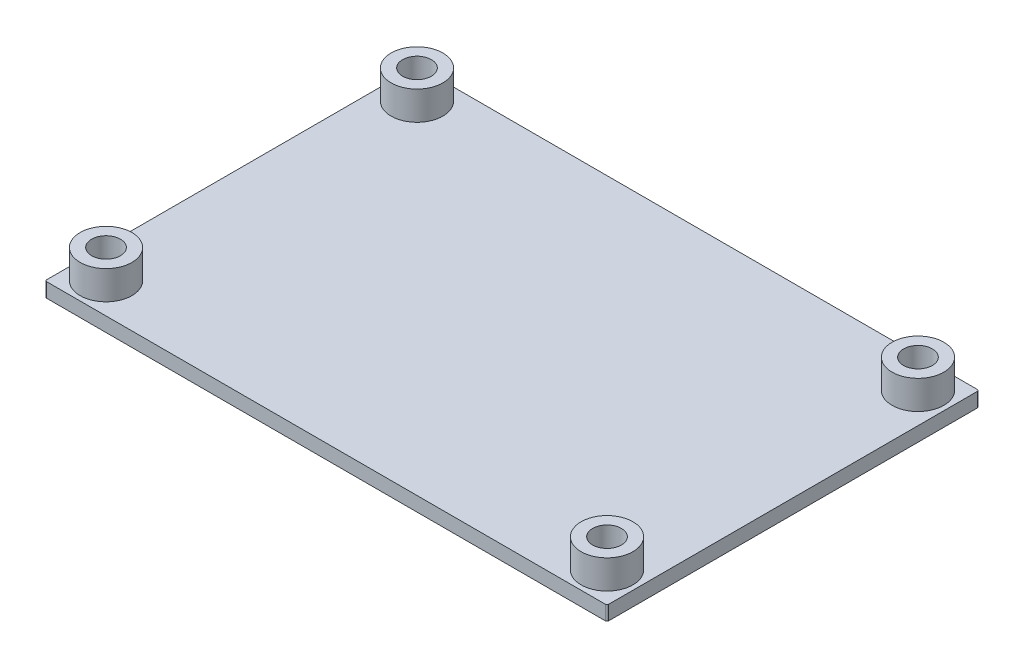
SolidWorks part; units mm, degrees
ref_plane "Front Plane" through (0, 0, 0) normal (0, 0, 1) x (1, 0, 0)
ref_plane "Top Plane" through (0, 0, 0) normal (0, 1, 0) x (1, 0, 0)
ref_plane "Right Plane" through (0, 0, 0) normal (1, 0, 0) x (0, 0, -1)
sketch "Sketch2" plane through (0, 0, 0) normal (0, 1, 0) x (1, 0, 0)
  line L0 (100.3, 3) -> (100.3, 67)
  line L1 (3, 0) -> (100, 0)
  line L2 (0, 3) -> (0, 67)
  line L3 (3, 70) -> (100, 70)
  line L4 (103, 3) -> (103, 67)
  line L5 (3, 67.3) -> (100, 67.3)
  line L6 (2.7, 3) -> (2.7, 67)
  line L7 (3, 2.7) -> (100, 2.7)
  line L8 (103, 35) -> (0, 35) construction
  line L9 (51.5, 70) -> (51.5, 0) construction
  arc A0 (0, 67) -> (3, 70) centre (3, 67) cw
  arc A1 (3, 0) -> (0, 3) centre (3, 3) cw
  arc A2 (100, 0) -> (103, 3) centre (100, 3) ccw
  arc A3 (100, 70) -> (103, 67) centre (100, 67) cw
  arc A4 (100, 67.3) -> (100.3, 67) centre (100, 67) cw
  arc A5 (2.7, 67) -> (3, 67.3) centre (3, 67) cw
  arc A6 (3, 2.7) -> (2.7, 3) centre (3, 3) cw
  arc A7 (100, 2.7) -> (100.3, 3) centre (100, 3) ccw
  circle A8 centre (95, 8) radius 2.5
  circle A9 centre (95, 8) radius 4.5
  circle A10 centre (95, 62) radius 2.5
  circle A11 centre (95, 62) radius 4.5
  circle A12 centre (8, 62) radius 4.5
  circle A13 centre (8, 62) radius 2.5
  circle A14 centre (8, 8) radius 2.5
  circle A15 centre (8, 8) radius 4.5
  point P9 (0, 0)
  point P12 (103, 0)
  point P15 (103, 70)
  dimension "D3" = 3
  dimension "D5" = 2
  dimension "D6" = 8
  dimension "D1" = 70
  dimension "D2" = 103
  dimension "D7" = 8
  dimension "D4" = 2.7
extrude "Boss-Extrude2" add sketch "Sketch2" along normal blind 7.5 contours A9 A8 | A11 A10 | A12 A13 | A15 A14 region at (90.6273, 0, -8) region at (90.6273, 0, -62) region at (3.6273, 0, -62) region at (3.6273, 0, -8)
extrude "Boss-Extrude4" add sketch "Sketch2<10>" along normal blind 2.5 contours L7 A7 L0 A4 L5 A5 L6 A6 A12 A9 A11 A15 | A14 | A13 | A8 | A10 region at (51.5, 0, -35) region at (95, 0, -8) region at (95, 0, -62) region at (8, 0, -62) region at (8, 0, -8)
sketch "Sketch2<10>" plane through (0, 0, 0) normal (0, 1, 0) x (1, 0, 0) same geometry as "Sketch2"
